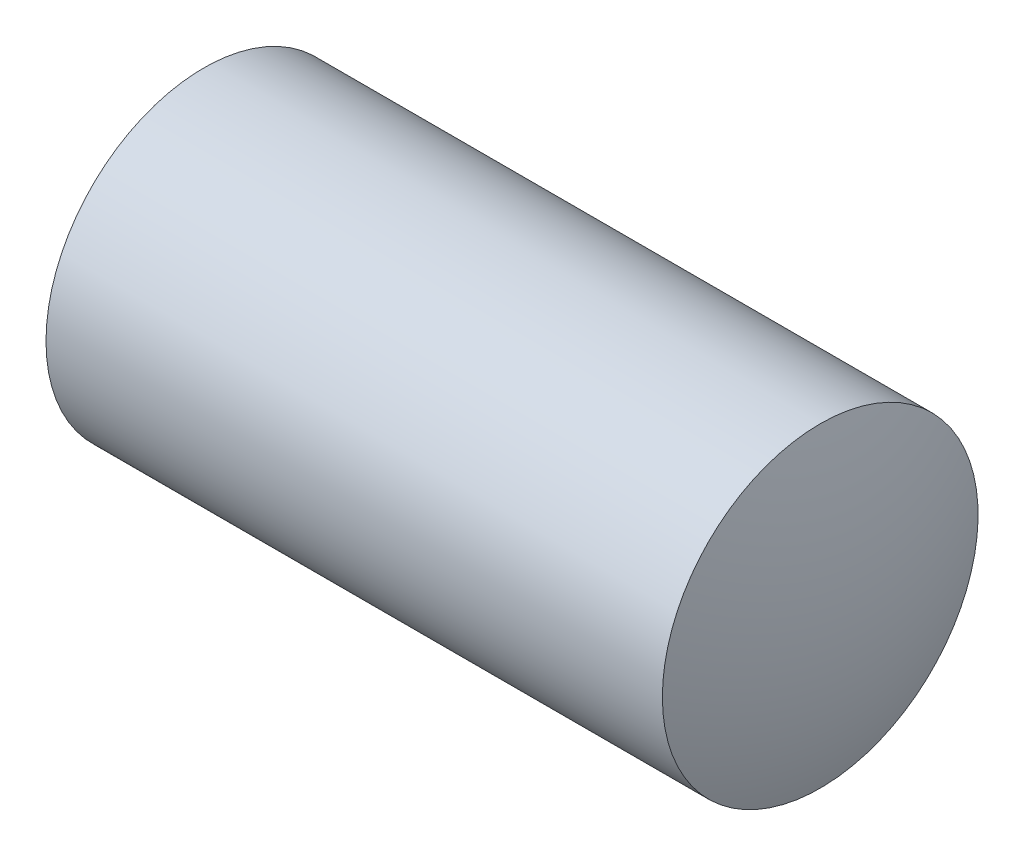
SolidWorks part; units mm, degrees
revolve "BaseBody" add sketch "BodySke" angle 360 about L5 other way angle 60
sketch "BodySke" plane through (0, 0, 0) normal (0, 0, 1) x (1, 0, 0)
  line L0 (0, 0) -> (0, 10.352)
  line L1 (0, 10.352) -> (0.9515, 12)
  line L2 (0.9515, 12) -> (47.8119, 12)
  line L3 (48.3857, 15.875) -> (48.3857, -3.175) construction
  line L4 (50, 0) -> (0, 0)
  line L5 (-12.7, 0) -> (88.9, 0) construction
  line L8 (0, -10.352) -> (0.9515, -12) construction
  line L9 (3, 15.875) -> (3, -3.175) construction
  arc A0 (50, 0) -> (47.8119, 12) centre (16, 0) ccw
  dimension "Length" = 50
  dimension "Diameter" = 24
cosmetic thread "ThreadCosmetic" [suppressed] parameters "Thread_minor"=20.704
ref_plane "Plane1" through (0, 0, 0) normal (0, 0, 1) x (1, 0, 0)
ref_plane "Plane2" through (0, 0, 0) normal (0, 1, 0) x (1, 0, 0)
ref_plane "Plane3" through (0, 0, 0) normal (1, 0, 0) x (0, 0, -1)
sketch "Sketch2" plane through (0, 0, 0) normal (-1, 0, 0) x (0, 0, 1)
  line L0 (3.4641, 6) -> (-3.4641, 6)
  line L1 (-3.4641, 6) -> (-6.9282, 0)
  line L2 (3.4641, 6) -> (6.9282, 0)
  line L3 (3.4641, -6) -> (6.9282, 0)
  line L4 (3.4641, -6) -> (-3.4641, -6)
  line L5 (-3.4641, -6) -> (-6.9282, 0)
  dimension "D2" = 6
  dimension "D3" = 6
extrude "Hex" cut sketch "Sketch2" against normal blind 15
sketch "ThdSchSke" plane through (0, 0, 0) normal (0, 0, 1) x (1, 0, 0)
  line L0 (0.9515, -10.352) -> (-0.2025, -12)
  line L1 (0.9515, -10.352) -> (2.1054, -12)
  line L2 (2.1054, -12) -> (2.1054, -15)
  line L3 (-3.175, 0) -> (5.1513, 0) construction
  line L5 (2.1054, -15) -> (-0.2025, -15)
  line L6 (-0.2025, -15) -> (-0.2025, -12)
  line L8 (0.9515, 12) -> (0.9515, -12) construction
  dimension "Thread_minor" = 20.704
  dimension "Diameter" = 24
revolve "ThreadSchematic" [suppressed] cut sketch "ThdSchSke" angle 360 about L3
pattern_linear "ThdSchPat" [suppressed]
equation "\"D2@Sketch2\" = \"Hex_size@Sketch2\" / 2"
equation "\"D3@Sketch2\" = \"Hex_size@Sketch2\" / 2"
equation "\"Thread_minor@ThreadCosmetic\" = \"Minor_dia@BodySke\""
equation "\"Thread_minor@ThdSchSke\" = \"Thread_minor@ThreadCosmetic\""
equation "\"Diameter@ThdSchSke\" = \"Diameter@BodySke\""
equation "\"Overcut@ThdSchSke\" = \"Diameter@BodySke\" * 1.25"
equation "\"Thread_len@BodySke\" = \"Length@BodySke\" -  ( ( ( \"Diameter@BodySke\" - \"Minor_dia@BodySke\" ) * 0.5 ) / tan( \"Drive_ch_ang@BodySke\" * 0.017453292 ) )"
equation "\"Thread_len@BodySke\" = \"Thread_len@BodySke\" - \"Oval_rad@BodySke\" + sqr(\"Oval_rad@BodySke\" * \"Oval_rad@BodySke\" - (\"Minor_dia@BodySke\" / 2) * (\"Minor_dia@BodySke\" / 2))"
equation "\"Num_threads@ThdSchPat\" = int( \"Thread_len@BodySke\" / \"Advance@BodySke\" + 0.999 )  + 1"
equation "\"Advance@ThdSchPat\" = \"Thread_len@BodySke\" /  (\"Num_threads@ThdSchPat\" - 1) 'relax it"
